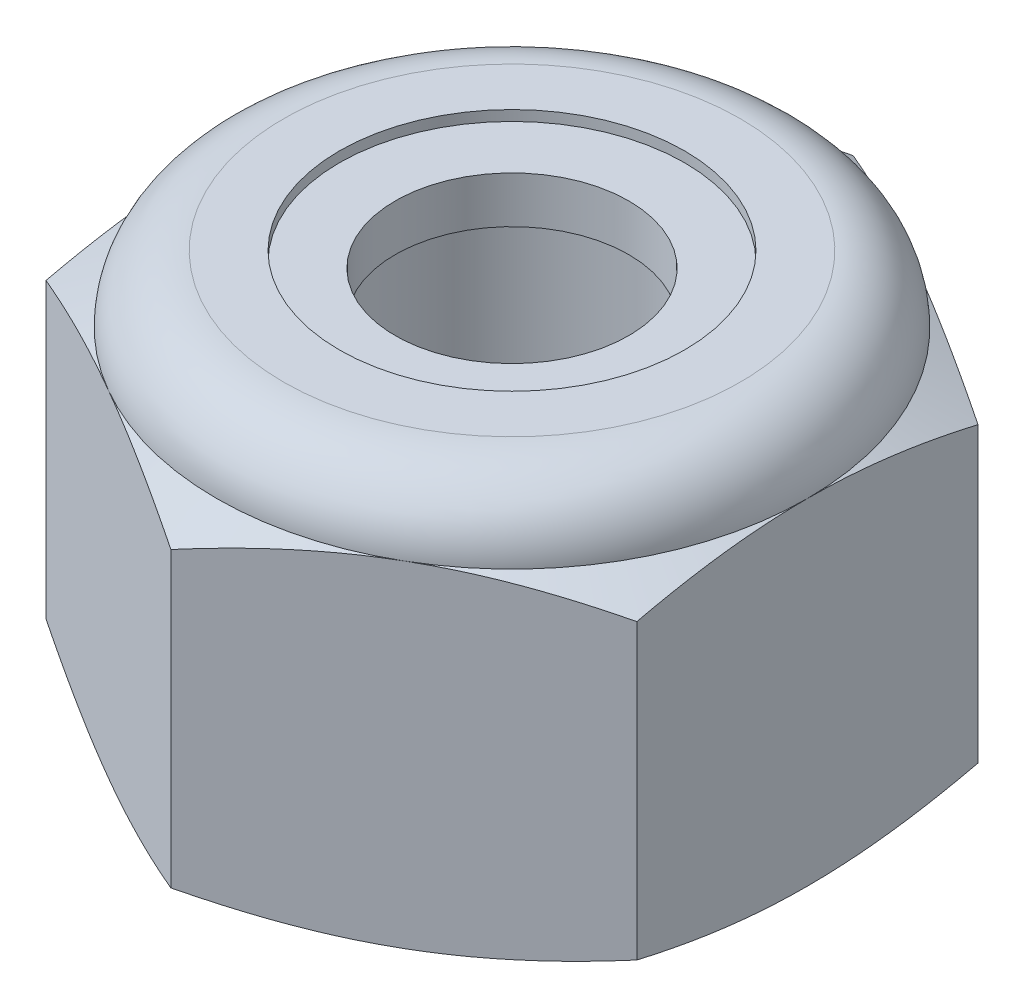
SolidWorks part; units mm, degrees
material "Plain Carbon Steel"
ref_plane "Front" through (0, 0, 0) normal (0, 0, 1) x (1, 0, 0)
ref_plane "Top" through (0, 0, 0) normal (0, 1, 0) x (1, 0, 0)
ref_plane "Right" through (0, 0, 0) normal (1, 0, 0) x (0, 0, -1)
sketch "Sketch1" plane through (0, 0, 0) normal (0, 1, 0) x (1, 0, 0)
  line L1 (0, 5.041) -> (-4.3656, 2.5205)
  line L2 (-4.3656, 2.5205) -> (-4.3656, -2.5205)
  line L3 (-4.3656, -2.5205) -> (0, -5.041)
  line L4 (0, -5.041) -> (4.3656, -2.5205)
  line L5 (4.3656, -2.5205) -> (4.3656, 2.5205)
  line L6 (4.3656, 2.5205) -> (0, 5.041)
  circle A0 centre (0, 0) radius 4.3656 construction
  dimension "Hex Flats" = 8.7312
extrude "Extrude1" add sketch "Sketch1" along normal blind 5.9531
sketch "Sketch2" plane through (0, 0, 0) normal (1, 0, 0) x (0, 0, -1)
  line L0 (-2.0828, 0) -> (-2.0828, 5.9531) construction
  line L1 (0, 0) -> (2.0828, 0)
  line L2 (0, 0) -> (0, 5.9531)
  line L3 (0, 5.9531) -> (2.0828, 5.9531)
  line L4 (2.0828, 0) -> (2.0828, 5.9531)
  line L5 (-2.5205, 5.9531) -> (2.5205, 5.9531) construction
  line L7 (0, -2.0828) -> (0, 0) construction
  dimension "Thread Dia" = 4.1656
revolve "Revolve1" add sketch "Sketch2" angle 360 about L7
sketch "Sketch3" plane through (0, 0, 0) normal (1, 0, 0) x (0, 0, -1)
  line L0 (2.0828, 5.9531) -> (-2.0828, 5.9531) construction
  line L1 (-2.0828, 5.9531) -> (-2.0828, 5.1594) construction
  line L2 (-2.0828, 5.1594) -> (2.0828, 5.9531) construction
  line L3 (2.0828, 5.9531) -> (2.1014, 5.8557) construction
  line L4 (2.1014, 5.8557) -> (2.2314, 5.1734)
  line L5 (2.2314, 5.1734) -> (1.7629, 5.3366)
  line L6 (1.7629, 5.3366) -> (1.7258, 5.5316)
  line L7 (1.7258, 5.5316) -> (2.1014, 5.8557)
  line L8 (1.7443, 5.4341) -> (2.1664, 5.5145) construction
  line L9 (2.0828, 5.9531) -> (2.0828, 5.4986) construction
  line L10 (2.0828, 5.4986) -> (-2.0828, 4.7049) construction
  line L11 (-2.0828, 4.7049) -> (-2.0828, 5.1594) construction
  line L12 (-0.1622, 5.9531) -> (0.1622, 4.2503) construction
  line L13 (-2.0828, 0) -> (-2.0828, 5.9531) construction
  line L14 (0, 5.9531) -> (2.0828, 5.9531) construction
  line L15 (2.0828, 0) -> (2.0828, 5.9531) construction
  point P13 (0, 5.1017)
  dimension "D1" = 0.0992
  dimension "D2" = 0.1984
  dimension "D4" = 60
  dimension "D5" = 0.7937
sketch "Sketch4" plane through (0, 0, 0) normal (1, 0, 0) x (0, 0, -1)
  line L0 (0, 5.9531) -> (2.0828, 5.9531)
  line L1 (2.0828, 5.9531) -> (1.7258, 5.7866)
  line L2 (1.7258, 5.7866) -> (1.7258, 0.1665)
  line L3 (1.7258, 0.1665) -> (2.0828, 0)
  line L4 (2.0828, 0) -> (0, 0)
  line L5 (0, 0) -> (0, 5.9531)
  line L6 (2.0828, 0) -> (2.0828, 5.9531) construction
  line L7 (0, 5.9531) -> (2.0828, 5.9531) construction
  line L8 (0, 0) -> (2.0828, 0) construction
  line L9 (0, 0) -> (0, 5.9531) construction
  line L10 (0, 5.9531) -> (0, 6.3471) construction
  dimension "D1" = 25
combine bodies "Combine1" operation type subtract main body 108 bodies to subtract 109
sketch "Sketch5" plane through (0, 0, 0) normal (1, 0, 0) x (0, 0, -1)
  line L0 (0, 0) -> (4.3656, 0)
  line L1 (4.3656, 0) -> (5.041, 0.3149)
  line L2 (5.041, 0.3149) -> (5.041, 4.646)
  line L3 (5.041, 4.646) -> (4.3656, 4.9609)
  line L4 (3.3734, 5.9531) -> (3.3734, 7.2231)
  line L5 (3.3734, 7.2231) -> (6.311, 7.2231)
  line L6 (6.311, 7.2231) -> (6.311, -1.27)
  line L7 (6.311, -1.27) -> (0, -1.27)
  line L8 (0, -1.27) -> (0, 0)
  line L9 (4.3656, 4.9609) -> (4.3656, 0) construction
  line L10 (0, 0) -> (2.0828, 0) construction
  line L13 (5.041, 2.4805) -> (6.311, 2.4805) construction
  line L14 (5.041, 5.9531) -> (5.041, 0) construction
  line L15 (0, 0) -> (0, 7.2231) construction
  line L20 (0, 7.2231) -> (3.3734, 7.2231) construction
  line L22 (0, 5.9531) -> (2.0828, 5.9531) construction
  arc A0 (4.3656, 4.9609) -> (3.3734, 5.9531) centre (3.3734, 4.9609) ccw
  dimension "D1" = 25
  dimension "D2" = 1.27
  dimension "D3" = 5.9531
  dimension "D4" = 0.9922
revolve "Cut-Revolve3" cut sketch "Sketch5" angle 360 about L15
sketch "Sketch6" plane through (0, 0, 0) normal (1, 0, 0) x (0, 0, -1)
  line L0 (0, 4.9609) -> (4.2132, 4.9609)
  line L1 (3.3734, 5.8007) -> (2.5496, 5.8007)
  line L2 (0, 7.2231) -> (0, 4.9609)
  line L3 (2.5496, 7.2231) -> (0, 7.2231)
  line L4 (0, 7.2231) -> (3.3734, 7.2231) construction
  line L5 (0, 0) -> (0, 7.2231) construction
  line L6 (0, 7.2231) -> (0, 44.323) construction
  line L7 (2.5496, 5.8007) -> (2.5496, 7.2231)
  line L8 (3.3734, 5.9531) -> (3.3734, 5.8007) construction
  line L9 (2.5496, 5.8007) -> (1.7258, 5.8007) construction
  line L10 (1.7258, 5.8007) -> (1.7258, 5.7866) construction
  arc A0 (4.2132, 4.9609) -> (3.3734, 5.8007) centre (3.3734, 4.9609) ccw
  arc A1 (4.3656, 4.9609) -> (3.3734, 5.9531) centre (3.3734, 4.9609) ccw construction
  dimension "D1" = 0.1524
revolve "Cut-Revolve4" cut sketch "Sketch6" angle 360 about L6
sketch "Sketch7" plane through (0, 0, 0) normal (1, 0, 0) x (0, 0, -1)
  line L0 (1.7258, 5.0371) -> (4.1332, 5.0371)
  line L1 (3.3734, 5.7245) -> (1.7258, 5.7245)
  line L2 (1.7258, 5.7245) -> (1.7258, 5.0371)
  line L3 (1.7258, 5.0371) -> (0, 5.0371) construction
  line L4 (0, 5.0371) -> (0, 5.7245) construction
  line L5 (0, 5.7245) -> (1.7258, 5.7245) construction
  line L6 (1.7258, 5.0371) -> (1.7258, 4.9609) construction
  line L7 (0, 4.9609) -> (4.2132, 4.9609) construction
  line L8 (3.3734, 5.7245) -> (3.3734, 5.8007) construction
  arc A0 (4.1332, 5.0371) -> (3.3734, 5.7245) centre (3.3734, 4.9609) ccw
  arc A2 (4.2132, 4.9609) -> (3.3734, 5.8007) centre (3.3734, 4.9609) ccw construction
  dimension "D1" = 0.0762
revolve "Revolve2" add sketch "Sketch7" angle 360 about L4
ref_axis "Axis1" through (0, 0, 0) along (0, 1, 0)
equation "\"D1@Sketch3\"=\"Thread Pitch@Sketch3\"/8"
equation "\"D2@Sketch3\"=\"Thread Pitch@Sketch3\"/4"
equation "\"D5@Sketch3\"=\"Thread Pitch@Sketch3\""
equation "\"D4@Sketch5\"=\"Height@Extrude1\"/6"
